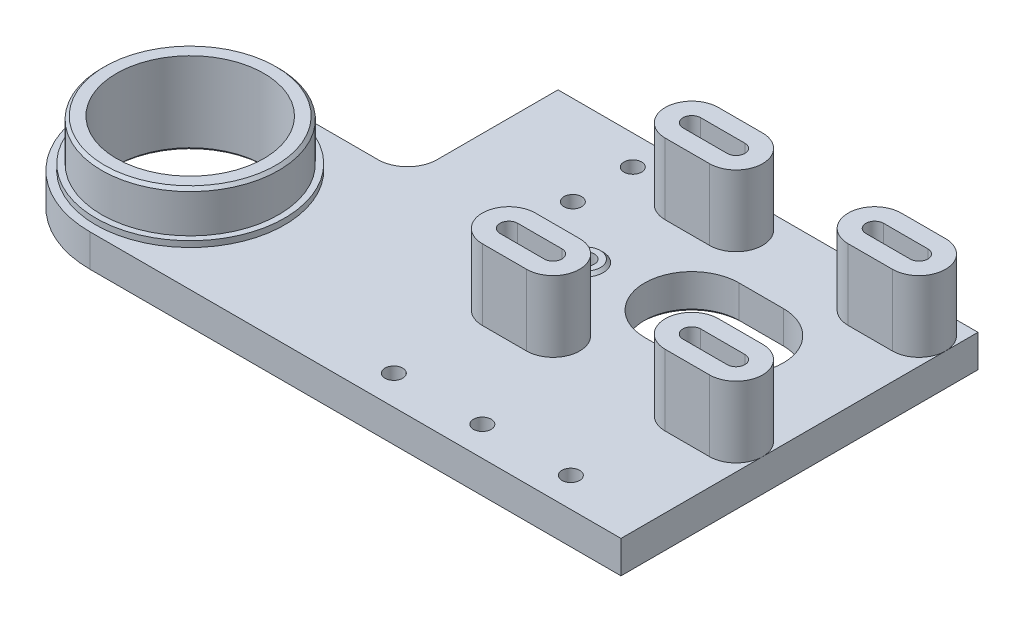
SolidWorks part; units mm, degrees
ref_plane "Front Plane" through (0, 0, 0) normal (0, 0, 1) x (1, 0, 0)
ref_plane "Top Plane" through (0, 0, 0) normal (0, 1, 0) x (1, 0, 0)
ref_plane "Right Plane" through (0, 0, 0) normal (1, 0, 0) x (0, 0, -1)
sketch "Sketch1" plane through (0, 0, 0) normal (0, 1, 0) x (1, 0, 0)
  line L0 (60.6181, 17.7752) -> (49.3328, 24.1377) construction
  line L2 (-17.5, 17.5) -> (-17.5, -17.5)
  line L5 (47.5, 37.5) -> (78.5, 37.5) construction
  line L6 (47.5, 37.5) -> (47.5, 6.5) construction
  line L7 (47.5, 6.5) -> (78.5, 6.5) construction
  line L8 (78.5, 37.5) -> (78.5, 6.5) construction
  line L9 (64.0945, 26.7249) -> (9.1398, 39.4552) construction
  line L10 (42.2652, 20.3799) -> (40.3703, -3.2389) construction
  line L11 (63, 22) -> (63, 43) construction
  line L12 (84, 43) -> (42, 43) construction
  line L13 (84, 43) -> (84, 1) construction
  line L14 (84, 1) -> (42, 1) construction
  line L15 (42, 43) -> (42, 1) construction
  line L16 (63, 22) -> (84, 22) construction
  line L17 (-12.5, -1000) -> (-12.5, 49000) construction
  line L18 (-1001.6818, 12.5) -> (48998.3182, 12.5) construction
  line L19 (-991.5, -12.5) -> (49008.5, -12.5) construction
  line L20 (-17.5, -17.5) -> (90.5, -17.5)
  line L21 (90.5, 43) -> (90.5, -17.5)
  line L23 (47.5, 37.5) -> (55, 37.5) construction
  line L24 (47.5, 39) -> (55, 39)
  line L25 (47.5, 36) -> (55, 36)
  line L26 (78.5, 37.5) -> (86, 37.5) construction
  line L27 (78.5, 39) -> (86, 39)
  line L28 (78.5, 36) -> (86, 36)
  line L29 (47.5, 6.5) -> (55, 6.5) construction
  line L30 (47.5, 8) -> (55, 8)
  line L31 (47.5, 5) -> (55, 5)
  line L32 (78.5, 6.5) -> (86, 6.5) construction
  line L33 (78.5, 8) -> (86, 8)
  line L34 (78.5, 5) -> (86, 5)
  line L35 (63, 22) -> (70.5, 22) construction
  line L36 (63, 30) -> (70.5, 30)
  line L37 (63, 14) -> (70.5, 14)
  line L40 (-17.5, 17.5) -> (19.3317, 17.5)
  line L41 (19.3317, 17.5) -> (19.3317, 43)
  line L42 (19.3317, 43) -> (90.5, 43)
  line L43 (87.5, -966.1083) -> (87.5, 49033.8917) construction
  line L44 (19.3317, 43) -> (-79.4, 43) construction
  line L45 (19.3317, 38) -> (90.5, 38) construction
  circle A0 centre (0, 0) radius 21 construction
  circle A1 centre (47.5, 37.5) radius 1.5 construction
  circle A2 centre (78.5, 37.5) radius 1.5 construction
  circle A3 centre (78.5, 6.5) radius 1.5 construction
  circle A4 centre (47.5, 6.5) radius 1.5 construction
  circle A5 centre (63, 22) radius 8 construction
  circle A9 centre (47, 20) radius 1.5
  circle A10 centre (47, 20) radius 6.5 construction
  circle A11 centre (0, 0) radius 42 construction
  arc A12 (40.3703, -3.2389) -> (9.1398, 39.4552) centre (0, 0) cw construction
  arc A13 (42.2652, 20.3799) -> (49.3328, 24.1377) centre (47, 20) cw construction
  arc A14 (64.0945, 26.7249) -> (60.6181, 17.7752) centre (63, 22) cw construction
  circle A15 centre (63, 22) radius 7 construction
  arc A16 (47.5, 39) -> (47.5, 36) centre (47.5, 37.5) ccw
  arc A17 (55, 36) -> (55, 39) centre (55, 37.5) ccw
  arc A18 (78.5, 39) -> (78.5, 36) centre (78.5, 37.5) ccw
  arc A19 (86, 36) -> (86, 39) centre (86, 37.5) ccw
  arc A20 (47.5, 8) -> (47.5, 5) centre (47.5, 6.5) ccw
  arc A21 (55, 5) -> (55, 8) centre (55, 6.5) ccw
  arc A22 (78.5, 8) -> (78.5, 5) centre (78.5, 6.5) ccw
  arc A23 (86, 5) -> (86, 8) centre (86, 6.5) ccw
  arc A24 (63, 30) -> (63, 14) centre (63, 22) ccw
  arc A25 (70.5, 14) -> (70.5, 30) centre (70.5, 22) ccw
  circle A26 centre (0, 0) radius 12.5
  circle A27 centre (47, -12.5) radius 1.5
  circle A28 centre (62, -12.5) radius 1.5
  circle A29 centre (77, -12.5) radius 1.5
  circle A30 centre (37, 38) radius 1.5
  circle A31 centre (37, 27.8373) radius 1.5
  point P17 (47.5, 22)
  point P18 (63, 37.5)
  point P19 (51.25, 37.5)
  point P27 (63, 43)
  point P47 (82.25, 37.5)
  point P56 (51.25, 6.5)
  point P62 (82.25, 6.5)
  point P68 (66.75, 22)
  point P92 (37, 27.8373)
  dimension "D1" = 42
  dimension "D2" = 16
  dimension "D4" = 3
  dimension "D5" = 40.5
  dimension "D6" = 4.85
  dimension "D7" = 4.75
  dimension "D9" = 3
  dimension "D14" = 13
  dimension "D15" = 84
  dimension "D13" = 14
  dimension "D18" = 25
  dimension "D23" = 3
  dimension "D3" = 31
  dimension "D8" = 42
  dimension "D10" = 5
  dimension "D11" = 5
  dimension "D12" = 3
  dimension "D16" = 7.5
  dimension "D17" = 5
  dimension "D19" = 63
  dimension "D20" = 44
  dimension "D21" = 20
  dimension "D22" = 47
  dimension "D24" = 5
  dimension "D26" = 5
  dimension "D27" = 5
  dimension "D25" = 3
extrude "Boss-Extrude1" add sketch "Sketch1" along normal blind 6
sketch "Sketch3" plane through (0, 6, 0) normal (0, 1, 0) x (1, 0, 0)
  line L0 (21, -1000) -> (21, 49000) construction
  line L9 (-12.5, -201000) -> (-12.5, 249000) construction
  line L10 (-201001.6818, 12.5) -> (248998.3182, 12.5) construction
  line L12 (21, -21) -> (-12.5, -21) construction
  line L13 (21, -21) -> (36, -21) construction
  circle A2 centre (0, 0) radius 21 construction
  circle A5 centre (-12.5, 12.5) radius 1.5
  circle A6 centre (21, 12.5) radius 1.5
  circle A9 centre (-12.5, -21) radius 1.5
  circle A10 centre (21, -21) radius 1.5
  point P32 (36, -20.7446)
  point P35 (35.2931, -40.5)
  dimension "D3" = 3
extrude "Cut-Extrude1" [suppressed] cut sketch "Sketch3" against normal through all
sketch "Sketch2" plane through (0, 6, 0) normal (0, -1, 0) x (1, 0, 0)
  circle A2 centre (0, 0) radius 16
  circle A3 centre (0, 0) radius 12.5 construction
  circle A4 centre (0, 0) radius 12.5
  point P5 (0, 0)
  dimension "D1" = 32
extrude "Boss-Extrude2" add sketch "Sketch2" against normal blind 1
sketch "Sketch6" plane through (0, 7, 0) normal (0, 1, 0) x (1, 0, 0)
  circle A0 centre (0, 0) radius 12.5 construction
  circle A1 centre (0, 0) radius 12.5
  circle A2 centre (0, 0) radius 15
  dimension "D1" = 30
fillet "Fillet1" [suppressed] radius 20
sketch "Sketch4" plane through (0, 6, 0) normal (0, 1, 0) x (1, 0, 0)
  line L0 (47.5, 37.5) -> (37.5, 37.5) construction
  line L1 (47.5, 36) -> (37.5, 36)
  line L2 (47.5, 39) -> (37.5, 39)
  line L3 (78.5, 37.5) -> (68.5, 37.5) construction
  line L4 (47.5, 37.5) -> (78.5, 37.5) construction
  line L5 (78.5, 36) -> (68.5, 36)
  line L6 (78.5, 39) -> (68.5, 39)
  line L7 (78.5, 6.5) -> (68.5, 6.5) construction
  line L8 (47.5, 6.5) -> (78.5, 6.5) construction
  line L9 (78.5, 5) -> (68.5, 5)
  line L10 (78.5, 8) -> (68.5, 8)
  line L11 (47.5, 6.5) -> (37.5, 6.5) construction
  line L12 (47.5, 5) -> (37.5, 5)
  line L13 (47.5, 8) -> (37.5, 8)
  line L14 (63, 22) -> (53, 22) construction
  line L15 (63, 14) -> (53, 14)
  line L16 (63, 30) -> (53, 30)
  arc A0 (47.5, 36) -> (47.5, 39) centre (47.5, 37.5) ccw
  arc A1 (37.5, 39) -> (37.5, 36) centre (37.5, 37.5) ccw
  arc A2 (78.5, 36) -> (78.5, 39) centre (78.5, 37.5) ccw
  arc A3 (68.5, 39) -> (68.5, 36) centre (68.5, 37.5) ccw
  arc A4 (78.5, 5) -> (78.5, 8) centre (78.5, 6.5) ccw
  arc A5 (68.5, 8) -> (68.5, 5) centre (68.5, 6.5) ccw
  arc A6 (47.5, 5) -> (47.5, 8) centre (47.5, 6.5) ccw
  arc A7 (37.5, 8) -> (37.5, 5) centre (37.5, 6.5) ccw
  arc A8 (63, 14) -> (63, 30) centre (63, 22) ccw
  arc A9 (53, 30) -> (53, 14) centre (53, 22) ccw
  circle A10 centre (47.5, 37.5) radius 1.5 construction
  circle A11 centre (63, 22) radius 8 construction
  point P3 (42.5, 37.5)
  point P8 (73.5, 37.5)
  point P18 (73.5, 6.5)
  point P28 (42.5, 6.5)
  point P36 (58, 22)
  dimension "D1" = 10
extrude "Cut-Extrude2" [suppressed] cut sketch "Sketch4" against normal through all
chamfer "Chamfer1" [suppressed] distance 3 angle 45
sketch "Sketch5" plane through (0, 6, 0) normal (0, 1, 0) x (1, 0, 0)
  circle A0 centre (47, 20) radius 1.5 construction
  circle A1 centre (47, 20) radius 1.5
  circle A2 centre (47, 20) radius 3.5
  dimension "D1" = 2
extrude "Boss-Extrude3" add sketch "Sketch5" along normal blind 0.5
chamfer "Chamfer3" distance 1 angle 45 1 edges at (47, 6.5, -16.5)
sketch "Sketch7" plane through (0, 6, 0) normal (0, 1, 0) x (1, 0, 0)
  line L0 (78.5, 2) -> (86, 2)
  line L1 (86, 11) -> (78.5, 11)
  line L2 (78.5, 5) -> (86, 5)
  line L3 (86, 8) -> (78.5, 8)
  line L4 (78.5, 5) -> (86, 5)
  line L5 (86, 8) -> (78.5, 8)
  line L6 (47.5, 5) -> (55, 5)
  line L7 (55, 8) -> (47.5, 8)
  line L8 (47.5, 5) -> (55, 5)
  line L9 (55, 8) -> (47.5, 8)
  line L10 (78.5, 36) -> (86, 36)
  line L11 (86, 39) -> (78.5, 39)
  line L12 (78.5, 36) -> (86, 36)
  line L13 (86, 39) -> (78.5, 39)
  line L14 (47.5, 36) -> (55, 36)
  line L15 (55, 39) -> (47.5, 39)
  line L16 (47.5, 36) -> (55, 36)
  line L17 (55, 39) -> (47.5, 39)
  line L18 (47.5, 2) -> (55, 2)
  line L19 (55, 11) -> (47.5, 11)
  line L20 (78.5, 33) -> (86, 33)
  line L21 (86, 42) -> (78.5, 42)
  line L22 (47.5, 33) -> (55, 33)
  line L23 (55, 42) -> (47.5, 42)
  arc A4 (86, 2) -> (86, 11) centre (86, 6.5) ccw
  arc A5 (78.5, 11) -> (78.5, 2) centre (78.5, 6.5) ccw
  arc A6 (78.5, 8) -> (78.5, 5) centre (78.5, 6.5) ccw
  arc A7 (86, 5) -> (86, 8) centre (86, 6.5) ccw
  arc A8 (78.5, 8) -> (78.5, 5) centre (78.5, 6.5) ccw
  arc A9 (86, 5) -> (86, 8) centre (86, 6.5) ccw
  arc A10 (47.5, 8) -> (47.5, 5) centre (47.5, 6.5) ccw
  arc A11 (55, 5) -> (55, 8) centre (55, 6.5) ccw
  arc A12 (47.5, 8) -> (47.5, 5) centre (47.5, 6.5) ccw
  arc A13 (55, 5) -> (55, 8) centre (55, 6.5) ccw
  arc A14 (78.5, 39) -> (78.5, 36) centre (78.5, 37.5) ccw
  arc A15 (86, 36) -> (86, 39) centre (86, 37.5) ccw
  arc A16 (78.5, 39) -> (78.5, 36) centre (78.5, 37.5) ccw
  arc A17 (86, 36) -> (86, 39) centre (86, 37.5) ccw
  arc A18 (47.5, 39) -> (47.5, 36) centre (47.5, 37.5) ccw
  arc A19 (55, 36) -> (55, 39) centre (55, 37.5) ccw
  arc A20 (47.5, 39) -> (47.5, 36) centre (47.5, 37.5) ccw
  arc A21 (55, 36) -> (55, 39) centre (55, 37.5) ccw
  arc A22 (55, 2) -> (55, 11) centre (55, 6.5) ccw
  arc A23 (47.5, 11) -> (47.5, 2) centre (47.5, 6.5) ccw
  arc A24 (86, 33) -> (86, 42) centre (86, 37.5) ccw
  arc A25 (78.5, 42) -> (78.5, 33) centre (78.5, 37.5) ccw
  arc A26 (55, 33) -> (55, 42) centre (55, 37.5) ccw
  arc A27 (47.5, 42) -> (47.5, 33) centre (47.5, 37.5) ccw
  dimension "D1" = 0
  dimension "D2" = 0
  dimension "D3" = 0
  dimension "D4" = 0
  dimension "D5" = 3
extrude "Boss-Extrude5" add sketch "Sketch7" along normal blind 12
fillet "Fillet4" [suppressed] radius 5
fillet "Fillet3" [suppressed] radius 5
fillet "Fillet5" radius 18 2 edges at (-17.5, 3, -17.5) (-17.5, 3, 17.5)
extrude "Boss-Extrude4" add sketch "Sketch6" along normal blind 7
chamfer "Chamfer5" distance 0.5 angle 45 1 edges at (0, 14, 15)
fillet "Fillet6" radius 5 1 edges at (19.3317, 3, -17.5)
chamfer "Chamfer2" distance 0.5 angle 45 35 edges at (47, 0, -18.5) (0, 0, 12.5) (56.5, 0, -6.5) (45.5, 0, 17.5) (90.5, 0, -12.75) (78.5, 0, -22) (87.5, 0, -6.5) (56.5, 0, -37.5) (87.5, 0, -37.5) (66.75, 0, -30) (66.75, 0, -14) (55, 0, -22) (51.25, 0, -8) (51.25, 0, -5) (46, 0, -6.5) (51.25, 0, -39) (51.25, 0, -36) (46, 0, -37.5) (82.25, 0, -39) (82.25, 0, -36) (77, 0, -37.5) (82.25, 0, -8) (82.25, 0, -5) (77, 0, -6.5) (54.9158, 0, -43) (19.3317, 0, -32.75) (7.4158, 0, -17.5) (-12.0499, 0, -12.4035) (-12.0499, 0, 12.4035) (17.8672, 0, -18.9645) (37, 0, -26.3373) (37, 0, -36.5) (77, 0, 14) (62, 0, 14) (47, 0, 14)
